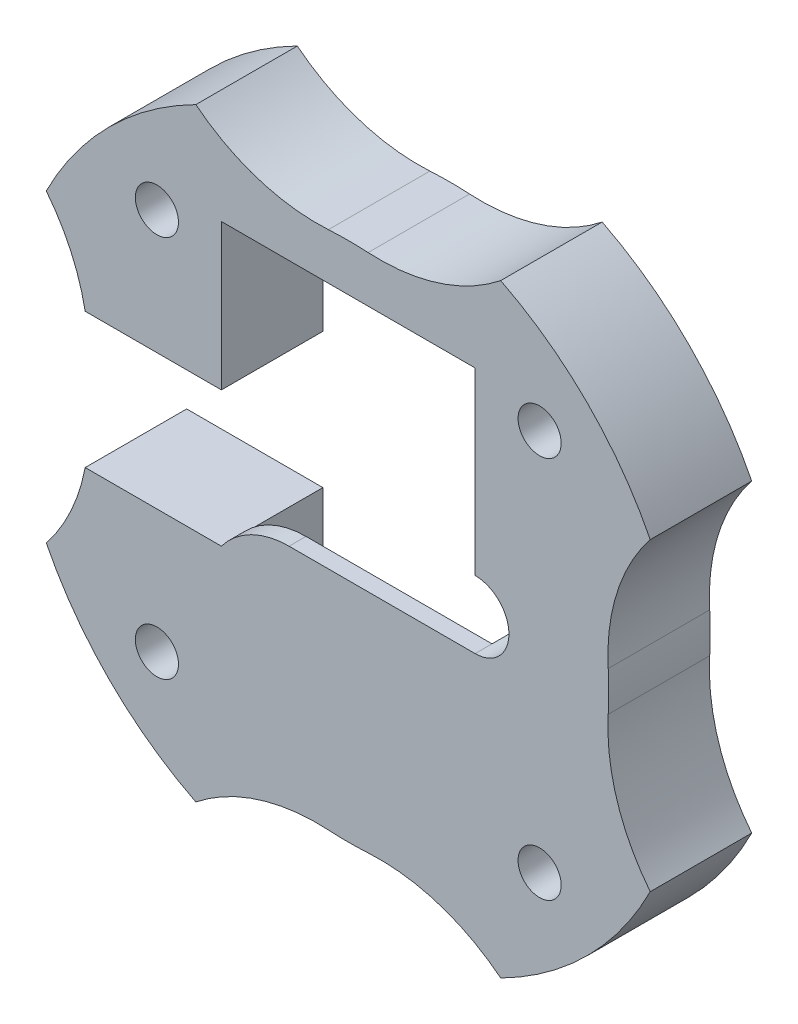
SolidWorks part; units mm, degrees
ref_plane "Front Plane" through (0, 0, 0) normal (0, 0, 1) x (1, 0, 0)
ref_plane "Top Plane" through (0, 0, 0) normal (0, 1, 0) x (1, 0, 0)
ref_plane "Right Plane" through (0, 0, 0) normal (1, 0, 0) x (0, 0, -1)
sketch "Sketch1" plane through (0, 0, 0) normal (0, 0, 1) x (1, 0, 0)
  line L0 (-15, 218.5) -> (-15, 199.25) construction
  line L1 (-15, 218.5) -> (-15, 199.25)
  line L2 (15, 245.75) -> (-15, 245.75) construction
  line L3 (15, 226.5) -> (15, 245.75) construction
  line L4 (15, 199.25) -> (15, 218.5) construction
  line L5 (-15, 199.25) -> (15, 199.25) construction
  line L6 (15, 245.75) -> (-15, 245.75)
  line L7 (15, 226.5) -> (15, 245.75)
  line L8 (15, 199.25) -> (15, 218.5)
  line L9 (-15, 199.25) -> (15, 199.25)
  line L10 (-15, 245.75) -> (-15, 226.5) construction
  line L11 (-15, 245.75) -> (-15, 226.5)
  circle A0 centre (-22.6274, 245.1274) radius 2.55 construction
  circle A1 centre (-22.6274, 245.1274) radius 2.55
  circle A2 centre (-22.6274, 199.8726) radius 2.55 construction
  circle A3 centre (-22.6274, 199.8726) radius 2.55
  circle A4 centre (22.6274, 199.8726) radius 2.55 construction
  circle A5 centre (22.6274, 199.8726) radius 2.55
  circle A6 centre (22.6274, 245.1274) radius 2.55 construction
  circle A7 centre (22.6274, 245.1274) radius 2.55
  arc A8 (-15, 226.5) -> (-15, 218.5) centre (-15, 222.5) ccw construction
  arc A9 (-15, 226.5) -> (-15, 218.5) centre (-15, 222.5) ccw
  arc A10 (15, 218.5) -> (15, 226.5) centre (15, 222.5) ccw construction
  arc A11 (15, 218.5) -> (15, 226.5) centre (15, 222.5) ccw
  arc A16 (18.0242, 186.791) -> (2.3471, 191.7594) centre (3.6966, 168.7998) ccw
  arc A17 (18.0242, 186.791) -> (35.709, 204.4758) centre (0, 222.5) ccw
  arc A18 (30.7406, 220.1529) -> (35.709, 204.4758) centre (53.7002, 218.8034) ccw
  arc A19 (30.7406, 220.1529) -> (30.7406, 224.8471) centre (-9.1905, 222.5) ccw
  arc A20 (35.709, 240.5242) -> (30.7406, 224.8471) centre (53.7002, 226.1966) ccw
  arc A21 (35.709, 240.5242) -> (18.0242, 258.209) centre (0, 222.5) ccw
  arc A22 (2.3471, 253.2406) -> (18.0242, 258.209) centre (3.6966, 276.2002) ccw
  arc A23 (2.3471, 253.2406) -> (-2.3471, 253.2406) centre (0, 213.3095) ccw
  arc A24 (-18.0242, 258.209) -> (-2.3471, 253.2406) centre (-3.6966, 276.2002) ccw
  arc A25 (-18.0242, 258.209) -> (-35.709, 240.5242) centre (0, 222.5) ccw
  arc A26 (-30.7406, 224.8471) -> (-35.709, 240.5242) centre (-53.7002, 226.1966) ccw
  arc A27 (-30.7406, 224.8471) -> (-30.7406, 220.1529) centre (9.1905, 222.5) ccw
  arc A28 (-35.709, 204.4758) -> (-30.7406, 220.1529) centre (-53.7002, 218.8034) ccw
  arc A29 (-35.709, 204.4758) -> (-18.0242, 186.791) centre (0, 222.5) ccw
  arc A30 (-2.3471, 191.7594) -> (-18.0242, 186.791) centre (-3.6966, 168.7998) ccw
  arc A31 (-2.3471, 191.7594) -> (2.3471, 191.7594) centre (0, 231.6905) ccw
  arc A32 (18.0242, 186.791) -> (2.3471, 191.7594) centre (3.6966, 168.7998) ccw
  arc A33 (18.0242, 186.791) -> (35.709, 204.4758) centre (0, 222.5) ccw
  arc A34 (30.7406, 220.1529) -> (35.709, 204.4758) centre (53.7002, 218.8034) ccw
  arc A35 (30.7406, 220.1529) -> (30.7406, 224.8471) centre (-9.1905, 222.5) ccw
  arc A36 (35.709, 240.5242) -> (30.7406, 224.8471) centre (53.7002, 226.1966) ccw
  arc A37 (35.709, 240.5242) -> (18.0242, 258.209) centre (0, 222.5) ccw
  arc A38 (2.3471, 253.2406) -> (18.0242, 258.209) centre (3.6966, 276.2002) ccw
  arc A39 (2.3471, 253.2406) -> (-2.3471, 253.2406) centre (0, 213.3095) ccw
  arc A40 (-18.0242, 258.209) -> (-2.3471, 253.2406) centre (-3.6966, 276.2002) ccw
  arc A41 (-18.0242, 258.209) -> (-35.709, 240.5242) centre (0, 222.5) ccw
  arc A42 (-30.7406, 224.8471) -> (-35.709, 240.5242) centre (-53.7002, 226.1966) ccw
  arc A43 (-30.7406, 224.8471) -> (-30.7406, 220.1529) centre (9.1905, 222.5) ccw
  arc A44 (-35.709, 204.4758) -> (-30.7406, 220.1529) centre (-53.7002, 218.8034) ccw
  arc A45 (-35.709, 204.4758) -> (-18.0242, 186.791) centre (0, 222.5) ccw
  arc A46 (-2.3471, 191.7594) -> (-18.0242, 186.791) centre (-3.6966, 168.7998) ccw
  arc A47 (-2.3471, 191.7594) -> (2.3471, 191.7594) centre (0, 231.6905) ccw
  dimension "D1" = 0
extrude "Boss-Extrude2" add sketch "Sketch1" along normal blind 10
sketch "Sketch2" plane through (0, 0, 10) normal (0, 0, 1) x (1, 0, 0)
  line L6 (-15, 245.75) -> (-15, 226.5) construction
  line L7 (15, 245.75) -> (-15, 245.75) construction
  line L8 (15, 226.5) -> (15, 245.75) construction
  line L9 (-15, 245.75) -> (-15, 226.5)
  line L10 (15, 245.75) -> (-15, 245.75)
  line L11 (15, 226.5) -> (15, 245.75)
  line L12 (-15, 218.5) -> (15, 218.5)
  arc A0 (-15, 226.5) -> (-15, 218.5) centre (-15, 222.5) ccw construction
  arc A1 (-15, 226.5) -> (-15, 218.5) centre (-15, 222.5) ccw
  arc A2 (15, 218.5) -> (15, 226.5) centre (15, 222.5) ccw construction
  arc A3 (15, 218.5) -> (15, 226.5) centre (15, 222.5) ccw
  circle A4 centre (-22.6274, 245.1274) radius 2.55 construction
  circle A5 centre (-22.6274, 245.1274) radius 2.55
  circle A6 centre (-22.6274, 199.8726) radius 2.55 construction
  circle A7 centre (-22.6274, 199.8726) radius 2.55
  circle A8 centre (22.6274, 199.8726) radius 2.55 construction
  circle A9 centre (22.6274, 199.8726) radius 2.55
  circle A10 centre (22.6274, 245.1274) radius 2.55 construction
  circle A11 centre (22.6274, 245.1274) radius 2.55
  arc A16 (18.0242, 186.791) -> (35.709, 204.4758) centre (0, 222.5) ccw
  arc A17 (30.7406, 220.1529) -> (35.709, 204.4758) centre (53.7002, 218.8034) ccw
  arc A18 (30.7406, 220.1529) -> (30.7406, 224.8471) centre (-9.1905, 222.5) ccw
  arc A19 (35.709, 240.5242) -> (30.7406, 224.8471) centre (53.7002, 226.1966) ccw
  arc A20 (35.709, 240.5242) -> (18.0242, 258.209) centre (0, 222.5) ccw
  arc A21 (2.3471, 253.2406) -> (18.0242, 258.209) centre (3.6966, 276.2002) ccw
  arc A22 (2.3471, 253.2406) -> (-2.3471, 253.2406) centre (0, 213.3095) ccw
  arc A23 (-18.0242, 258.209) -> (-2.3471, 253.2406) centre (-3.6966, 276.2002) ccw
  arc A24 (-18.0242, 258.209) -> (-35.709, 240.5242) centre (0, 222.5) ccw
  arc A25 (-30.7406, 224.8471) -> (-35.709, 240.5242) centre (-53.7002, 226.1966) ccw
  arc A26 (-30.7406, 224.8471) -> (-30.7406, 220.1529) centre (9.1905, 222.5) ccw
  arc A27 (-35.709, 204.4758) -> (-30.7406, 220.1529) centre (-53.7002, 218.8034) ccw
  arc A28 (-35.709, 204.4758) -> (-18.0242, 186.791) centre (0, 222.5) ccw
  arc A29 (-2.3471, 191.7594) -> (-18.0242, 186.791) centre (-3.6966, 168.7998) ccw
  arc A30 (-2.3471, 191.7594) -> (2.3471, 191.7594) centre (0, 231.6905) ccw
  arc A31 (18.0242, 186.791) -> (2.3471, 191.7594) centre (3.6966, 168.7998) ccw
  arc A32 (18.0242, 186.791) -> (35.709, 204.4758) centre (0, 222.5) ccw
  arc A33 (30.7406, 220.1529) -> (35.709, 204.4758) centre (53.7002, 218.8034) ccw
  arc A34 (30.7406, 220.1529) -> (30.7406, 224.8471) centre (-9.1905, 222.5) ccw
  arc A35 (35.709, 240.5242) -> (30.7406, 224.8471) centre (53.7002, 226.1966) ccw
  arc A36 (35.709, 240.5242) -> (18.0242, 258.209) centre (0, 222.5) ccw
  arc A37 (2.3471, 253.2406) -> (18.0242, 258.209) centre (3.6966, 276.2002) ccw
  arc A38 (2.3471, 253.2406) -> (-2.3471, 253.2406) centre (0, 213.3095) ccw
  arc A39 (-18.0242, 258.209) -> (-2.3471, 253.2406) centre (-3.6966, 276.2002) ccw
  arc A40 (-18.0242, 258.209) -> (-35.709, 240.5242) centre (0, 222.5) ccw
  arc A41 (-30.7406, 224.8471) -> (-35.709, 240.5242) centre (-53.7002, 226.1966) ccw
  arc A42 (-30.7406, 224.8471) -> (-30.7406, 220.1529) centre (9.1905, 222.5) ccw
  arc A43 (-35.709, 204.4758) -> (-30.7406, 220.1529) centre (-53.7002, 218.8034) ccw
  arc A44 (-35.709, 204.4758) -> (-18.0242, 186.791) centre (0, 222.5) ccw
  arc A45 (-2.3471, 191.7594) -> (-18.0242, 186.791) centre (-3.6966, 168.7998) ccw
  arc A46 (-2.3471, 191.7594) -> (2.3471, 191.7594) centre (0, 231.6905) ccw
  arc A47 (18.0242, 186.791) -> (2.3471, 191.7594) centre (3.6966, 168.7998) ccw
  dimension "D2" = 19.25
  dimension "D1" = 0
extrude "Boss-Extrude3" add sketch "Sketch2" along normal blind 2
sketch "Sketch3" plane through (0, 0, 12) normal (0, 0, 1) x (1, 0, 0)
  line L0 (-15, 245.75) -> (15, 245.75)
  line L1 (15, 245.75) -> (15, 247.75)
  line L2 (15, 247.75) -> (-15, 247.75)
  line L3 (-15, 247.75) -> (-15, 245.75)
  dimension "D1" = 2
extrude "Cut-Extrude1" cut sketch "Sketch3" against normal blind 35
sketch "Sketch4" plane through (0, 0, 0) normal (0, 0, -1) x (-1, 0, 0)
  line L0 (19, 222.5) -> (30.8095, 222.5) construction
  line L5 (15, 218.5) -> (15, 199.25) construction
  line L6 (34.8095, 230.5) -> (15, 230.5)
  line L7 (34.8095, 230.5) -> (34.8095, 214.5)
  line L8 (34.8095, 214.5) -> (15, 214.5)
  line L9 (15, 230.5) -> (15, 214.5)
  line L10 (34.8095, 230.5) -> (15, 214.5) construction
  line L11 (34.8095, 214.5) -> (15, 230.5) construction
  arc A0 (15, 218.5) -> (15, 226.5) centre (15, 222.5) ccw construction
  arc A1 (30.7406, 220.1529) -> (30.7406, 224.8471) centre (-9.1905, 222.5) ccw construction
  point P9 (24.9048, 222.5)
  dimension "D1" = 16
extrude "Cut-Extrude2" cut sketch "Sketch4" against normal blind 19
fillet "Fillet1" radius 10 1 edges at (-15, 218.5, 11)
